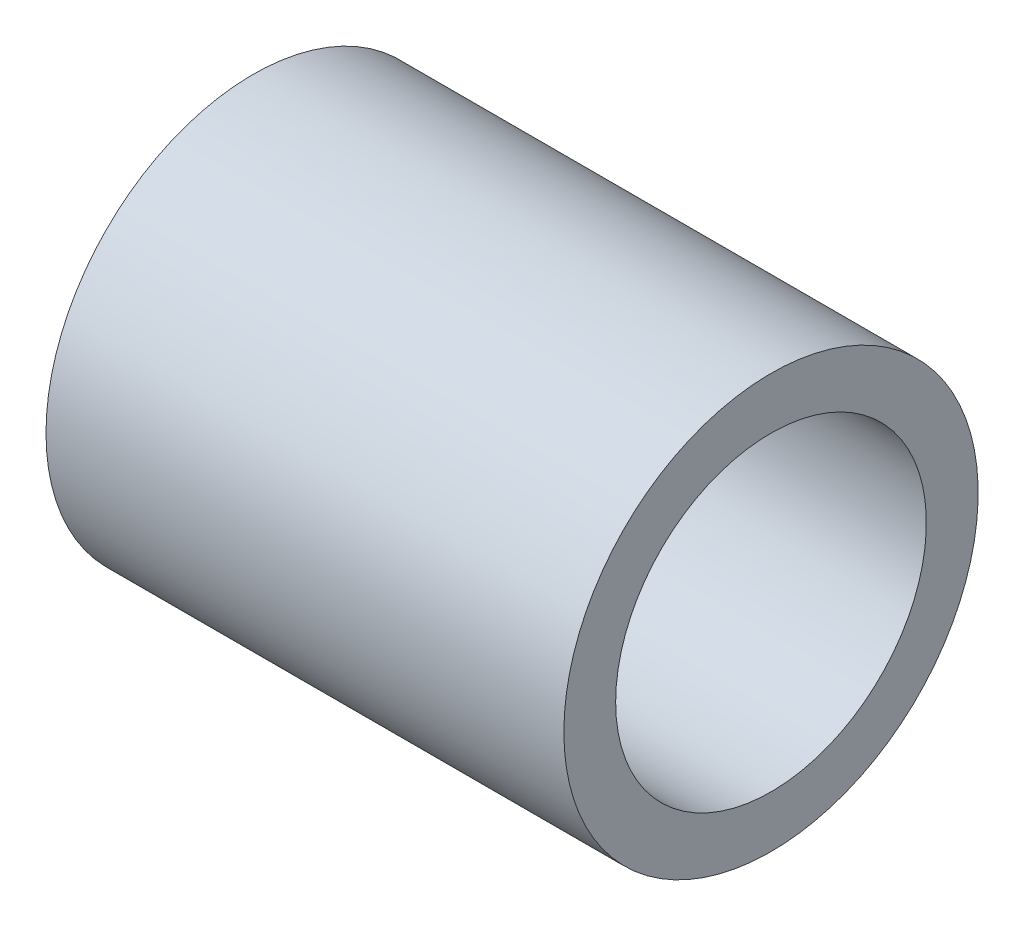
SolidWorks part; units mm, degrees
ref_plane "Front Plane" through (0, 0, 0) normal (0, 0, 1) x (1, 0, 0)
ref_plane "Top Plane" through (0, 0, 0) normal (0, 1, 0) x (1, 0, 0)
ref_plane "Right Plane" through (0, 0, 0) normal (1, 0, 0) x (0, 0, -1)
sketch "Bushing Sketch" plane through (0, 0, 0) normal (0, 0, 1) x (1, 0, 0)
  line L0 (-1000, 0) -> (1000, 0) construction
  line L1 (80, 3) -> (80, 4)
  line L2 (80, 4) -> (90, 4)
  line L3 (90, 4) -> (90, 3)
  line L4 (90, 3) -> (80, 3)
revolve "Bushing" add sketch "Bushing Sketch" angle 360 about L0
ref_axis "Engine Axis" through (90.5, 0, 0) along (-1, 0, 0)
